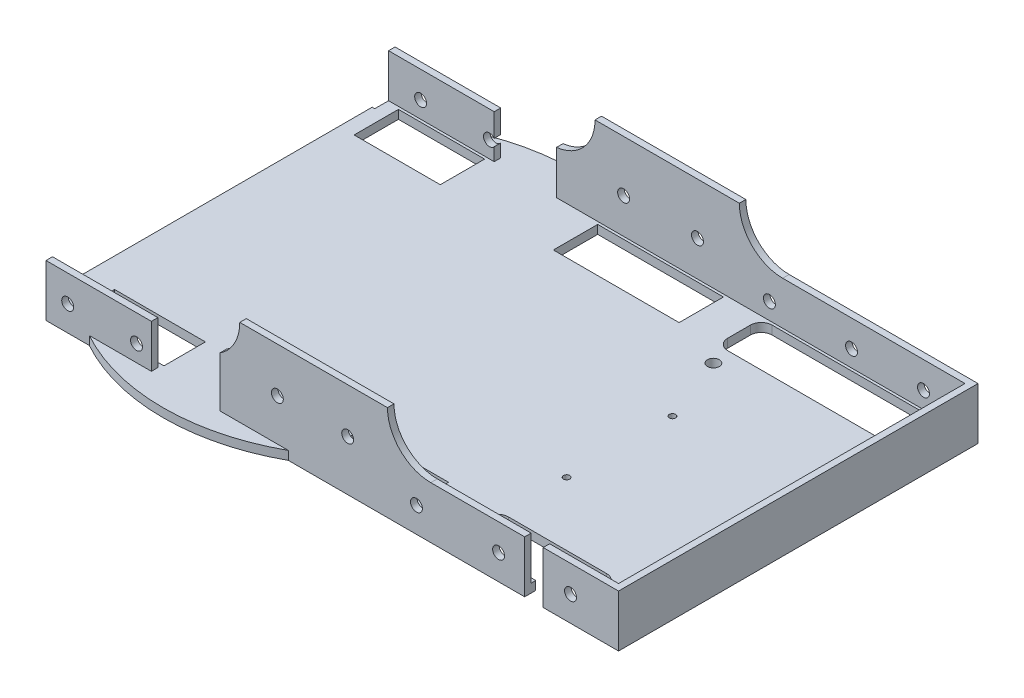
SolidWorks part; units mm, degrees
ref_plane "Front Plane" through (0, 0, 0) normal (0, 0, 1) x (1, 0, 0)
ref_plane "Top Plane" through (0, 0, 0) normal (0, 1, 0) x (1, 0, 0)
ref_plane "Right Plane" through (0, 0, 0) normal (1, 0, 0) x (0, 0, -1)
sketch "Sketch1" plane through (0, 0, 0) normal (0, 1, 0) x (1, 0, 0)
  line L1 (0, 0) -> (278.0499, 0)
  line L2 (0, 0) -> (0, 166.0007)
  line L3 (0, 166.0007) -> (278.0499, 166.0007)
  line L4 (278.0499, 0) -> (278.0499, 166.0007)
extrude "Boss-Extrude1" add sketch "Sketch1" along normal blind 24
sketch "Sketch2" plane through (0, 0, 0) normal (0, -1, 0) x (-1, 0, 0)
  line L1 (-7.6506, 156.6405) -> (14.2402, 156.6405)
  line L2 (-7.6506, 156.6405) -> (-7.6506, 11.5417)
  line L3 (-7.6506, 11.5417) -> (14.2402, 11.5417)
  line L4 (14.2402, 156.6405) -> (14.2402, 11.5417)
extrude "Cut-Extrude1" cut sketch "Sketch2" against normal through all
sketch "Sketch3" plane through (0, 24, 0) normal (0, 1, 0) x (1, 0, 0)
  line L0 (226.9955, 0) -> (226.9955, 3) construction
  line L1 (0, 0) -> (278.0499, 0) construction
  line L2 (278.0499, 166.0007) -> (278.0499, 163.0007) construction
  line L3 (278.0499, 0) -> (278.0499, 166.0007) construction
  line L4 (0, 155.7398) -> (3, 155.7398) construction
  line L5 (0, 166.0007) -> (0, 156.6405) construction
  line L6 (278.0499, 22.4963) -> (275.0499, 22.4963) construction
  line L7 (275.0499, 163.0007) -> (275.0499, 3)
  line L8 (275.0499, 3) -> (3, 3)
  line L9 (3, 3) -> (3, 163.0007)
  line L10 (3, 163.0007) -> (275.0499, 163.0007)
extrude "Cut-Extrude2" cut sketch "Sketch3" against normal blind 20
sketch "Sketch4" plane through (0, 24, 0) normal (0, 1, 0) x (1, 0, 0)
  line L0 (0, 0) -> (278.0499, 0) construction
  line L1 (171.3453, 0) -> (103.1403, 0)
  line L2 (171.3453, 0) -> (171.3453, 3)
  line L3 (171.3453, 3) -> (103.1403, 3)
  line L4 (103.1403, 0) -> (103.1403, 3)
  line L5 (3, 3) -> (275.0499, 3) construction
extrude "Boss-Extrude2" add sketch "Sketch4" along normal blind 20
fillet "Fillet4" radius 20 1 edges at (103.1403, 24, -1.5) type face fillet first side face at (103.1403, 34, -1.5) second side face at (35.3801, 24, -4.8472)
fillet "Fillet5" radius 20 1 edges at (171.3453, 24, -1.5) type face fillet first side face at (145.489, 24, -97.7284) second side face at (171.3453, 34, -1.5)
sketch "Sketch5" plane through (0, 24, 0) normal (0, 1, 0) x (1, 0, 0)
  line L0 (278.0499, 166.0007) -> (0, 166.0007) construction
  line L1 (104.1867, 166.0007) -> (170.8443, 166.0007)
  line L2 (104.1867, 166.0007) -> (104.1867, 163.0007)
  line L3 (104.1867, 163.0007) -> (170.8443, 163.0007)
  line L4 (170.8443, 166.0007) -> (170.8443, 163.0007)
  line L5 (275.0499, 163.0007) -> (3, 163.0007) construction
extrude "Boss-Extrude3" add sketch "Sketch5" along normal blind 20
fillet "Fillet6" radius 20 1 edges at (104.1867, 24, -164.5007) type face fillet first side face at (104.1867, 34, -164.5007) second side face at (35.7289, 24, -161.8806)
fillet "Fillet7" radius 20 1 edges at (170.8443, 24, -164.5007) type face fillet first side face at (170.8443, 34, -164.5007) second side face at (228.8223, 24, -83.0003)
sketch "Sketch6" plane through (0, 0, -163.0007) normal (0, 0, 1) x (1, 0, 0)
  circle A0 centre (151.5064, 20.306) radius 2.75
  circle A1 centre (117.3926, 20.306) radius 2.75
extrude "HolesForBolts1" cut sketch "Sketch6" against normal through all
sketch "Sketch7" plane through (0, 0, -166.0007) normal (0, 0, -1) x (-1, 0, 0)
  circle A0 centre (-23.6542, 11.6758) radius 2.75
  circle A1 centre (-55.4415, 11.6758) radius 2.75
  circle A2 centre (-83.0044, 11.6758) radius 2.75
  circle A3 centre (-184.7276, 11.6758) radius 2.75
  circle A4 centre (-222.6455, 11.6758) radius 2.75
  circle A5 centre (-255.8817, 11.6758) radius 2.75
extrude "Cut-Extrude4" cut sketch "Sketch7" against normal through all
sketch "Sketch8" plane through (0, 0, -3) normal (0, 0, -1) x (-1, 0, 0)
  circle A0 centre (-120.4871, 23.2804) radius 2.75
  circle A1 centre (-152.9663, 23.2804) radius 2.75
extrude "Cut-Extrude5" cut sketch "Sketch8" against normal blind 20
ref_plane "Plane1" through (0, 0, -11.5417) normal (0, 0, 1) x (1, 0, 0)
sketch "Sketch11" plane through (0, 0, 0) normal (0, -1, 0) x (1, 0, 0)
  line L0 (7.6506, -11.5417) -> (0, -11.5417) construction
  line L1 (0, 0) -> (13.6461, 0)
  line L2 (0, 0) -> (0, -11.5417)
  line L3 (0, -11.5417) -> (13.6461, -11.5417)
  line L4 (13.6461, 0) -> (13.6461, -11.5417)
extrude "Cut-Extrude6" cut sketch "Sketch11" against normal through all
sketch "Sketch12" plane through (0, 0, 0) normal (0, -1, 0) x (1, 0, 0)
  line L0 (0, -156.6405) -> (7.6506, -156.6405) construction
  line L1 (0, -166.0007) -> (8.8441, -166.0007)
  line L2 (0, -166.0007) -> (0, -156.6405)
  line L3 (0, -156.6405) -> (8.8441, -156.6405)
  line L4 (8.8441, -166.0007) -> (8.8441, -156.6405)
extrude "Cut-Extrude7" cut sketch "Sketch12" against normal through all
sketch "HolesInLidForPiCover" plane through (0, 0, 0) normal (0, -1, 0) x (1, 0, 0)
  circle A0 centre (223.0138, -141.6086) radius 2.75
  circle A1 centre (223.0138, -22.1297) radius 2.75
ref_point "RasPiBoltPoint2"
ref_point "RasPiBoltPoint3"
ref_point "RasPiBoltPoint4"
sketch "LidHolesForPi" plane through (0, 0, 0) normal (0, -1, 0) x (1, 0, 0)
  circle A0 centre (200.5621, -102.3707) radius 1.455
  circle A1 centre (200.5621, -53.5029) radius 1.455
  circle A2 centre (258.5449, -53.5029) radius 1.455
  circle A3 centre (258.5449, -102.3707) radius 1.455
extrude "Cut-Extrude9" cut sketch "LidHolesForPi" against normal up to surface (4 mm away) up to face at (76.2977, 4, -83.5457)
ref_point "LidHoleForCoverLocation1"
ref_point "LidHoleForCoverLocation2"
sketch "Sketch14" plane through (0, 0, 0) normal (0, -1, 0) x (1, 0, 0)
  circle A0 centre (264.7636, -18.9201) radius 2.75
  circle A1 centre (181.6168, -18.9187) radius 2.75
extrude "Cut-Extrude10" cut sketch "Sketch14" against normal up to surface (4 mm away) up to face at (258.5449, 4, -54.9579)
sketch "Sketch15" plane through (0, 0, 1.7414) normal (0, -1, 0) x (1, 0, 0)
  circle A0 centre (79.5908, -84.8811) radius 95
extrude "PingPongHolder" add sketch "Sketch15" against normal up to surface (4 mm away) up to face at (181.6168, 4, -21.6687)
sketch "Sketch16" plane through (0, 0, 0) normal (0, -1, 0) x (1, 0, 0)
  line L1 (7.6506, -21.0945) -> (-30.4108, -21.0945)
  line L2 (7.6506, -21.0945) -> (7.6506, -147.5505)
  line L3 (7.6506, -147.5505) -> (-30.4108, -147.5505)
  line L4 (-30.4108, -21.0945) -> (-30.4108, -147.5505)
extrude "Cut-Extrude11" cut sketch "Sketch16" against normal up to surface (4 mm away) up to face at (60.2623, 4, -83.4645)
sketch "Sketch17" plane through (0, 0, 0) normal (0, -1, 0) x (1, 0, 0)
  line L1 (182.1244, -161.8248) -> (267.0462, -161.8248)
  line L2 (182.1244, -161.8248) -> (182.1244, -141.3482)
  line L3 (182.1244, -141.3482) -> (267.0462, -141.3482)
  line L4 (267.0462, -161.8248) -> (267.0462, -141.3482)
  line L5 (164.6719, -141.3482) -> (106.6019, -141.3482)
  line L6 (164.6719, -141.3482) -> (164.6719, -161.8248)
  line L7 (164.6719, -161.8248) -> (106.6019, -161.8248)
  line L8 (106.6019, -141.3482) -> (106.6019, -161.8248)
  line L13 (54.374, -141.3482) -> (14.584, -141.3482)
  line L14 (54.374, -141.3482) -> (54.374, -161.8248)
  line L15 (54.374, -161.8248) -> (14.584, -161.8248)
  line L16 (14.584, -141.3482) -> (14.584, -161.8248)
extrude "Cut-Extrude12" cut sketch "Sketch17" against normal up to surface (4 mm away) up to face at (76.2977, 4, -83.5457)
fillet "Fillet8" radius 5 1 edges at (182.1244, 2, -161.8248) type face fillet first side face at (182.1244, 2, -151.5865) second side face at (224.5853, 2, -161.8248)
fillet "Fillet9" radius 5 1 edges at (182.1244, 2, -141.3482) type face fillet first side face at (182.1244, 2, -149.0865) second side face at (224.5853, 2, -141.3482)
fillet "Fillet10" radius 5 1 edges at (267.0462, 2, -161.8248) type face fillet first side face at (227.0853, 2, -161.8248) second side face at (267.0462, 2, -151.5865)
fillet "Fillet11" radius 5 1 edges at (267.0462, 2, -141.3482) type face fillet first side face at (227.0853, 2, -141.3482) second side face at (267.0462, 2, -149.0865)
sketch "Sketch18" plane through (0, 0, 0) normal (0, -1, 0) x (1, 0, 0)
  line L1 (197.9754, -5.1076) -> (253.3194, -5.1076)
  line L2 (197.9754, -5.1076) -> (197.9754, -24.2435)
  line L3 (197.9754, -24.2435) -> (253.3194, -24.2435)
  line L4 (253.3194, -5.1076) -> (253.3194, -24.2435)
  line L5 (175.294, -5.1076) -> (134.149, -5.1076)
  line L6 (175.294, -5.1076) -> (175.294, -24.2435)
  line L7 (175.294, -24.2435) -> (134.149, -24.2435)
  line L8 (134.149, -5.1076) -> (134.149, -24.2435)
  line L13 (63.0138, -5.1076) -> (21.0604, -5.1076)
  line L14 (63.0138, -5.1076) -> (63.0138, -24.2435)
  line L15 (63.0138, -24.2435) -> (21.0604, -24.2435)
  line L16 (21.0604, -5.1076) -> (21.0604, -24.2435)
extrude "Cut-Extrude13" cut sketch "Sketch18" against normal up to surface (4 mm away) up to face at (135.6369, 4, -151.5865)
fillet "Fillet12" radius 5 1 edges at (197.9754, 2, -5.1076) type face fillet first side face at (197.9754, 2, -14.6756) second side face at (225.6474, 2, -5.1076)
fillet "Fillet13" radius 5 1 edges at (197.9754, 2, -24.2435) type face fillet first side face at (197.9754, 2, -17.1756) second side face at (225.6474, 2, -24.2435)
fillet "Fillet14" radius 5 1 edges at (253.3194, 2, -24.2435) type face fillet first side face at (228.1474, 2, -24.2435) second side face at (253.3194, 2, -14.6756)
fillet "Fillet15" radius 5 1 edges at (253.3194, 2, -5.1076) type face fillet first side face at (253.3194, 2, -12.1756) second side face at (228.1474, 2, -5.1076)
sketch "Sketch19" plane through (0, 0, 0) normal (0, -1, 0) x (1, 0, 0)
sketch "Sketch20" plane through (0, 0, 0) normal (0, 0, 1) x (1, 0, 0)
  line L0 (191.3453, 24) -> (278.0499, 24) construction
  line L1 (243.2334, 24) -> (234.6976, 24)
  line L2 (243.2334, 24) -> (243.2334, 0)
  line L3 (243.2334, 0) -> (234.6976, 0)
  line L4 (234.6976, 24) -> (234.6976, 0)
  line L5 (125.5559, 0) -> (278.0499, 0) construction
extrude "Cut-Extrude14" cut sketch "Sketch20" against normal up to surface (5.1076 mm away) up to face at (225.6474, 2, -5.1076)
sketch "Sketch21" plane through (0, 0, 0) normal (0, -1, 0) x (1, 0, 0)
  circle A0 centre (188.7854, -133.0569) radius 2.75
  circle A1 centre (188.0519, -10.1727) radius 2.75
  circle A2 centre (271.9321, -133.0569) radius 2.75
  circle A3 centre (269.9307, -9.7027) radius 2.75
extrude "Cut-Extrude15" cut sketch "Sketch21" against normal up to surface (4 mm away) up to face at (154.7215, 4, -14.6756)
sketch "Sketch22" plane through (0, 24, 0) normal (0, 1, 0) x (1, 0, 0)
  line L0 (13.6461, 0) -> (83.1403, 0) construction
  line L1 (62.3106, 0) -> (93.919, 0)
  line L2 (62.3106, 0) -> (62.3106, 3.4355)
  line L3 (62.3106, 3.4355) -> (93.919, 3.4355)
  line L4 (93.919, 0) -> (93.919, 3.4355)
extrude "Cut-Extrude16" cut sketch "Sketch22" against normal up to surface and the other way up to surface up to face at (79.5908, 4, 5.9302) other way up to face at (137.2428, 44, -1.5)
sketch "Sketch23" plane through (0, 24, 0) normal (0, 1, 0) x (1, 0, 0)
  line L0 (84.1867, 166.0007) -> (8.8441, 166.0007) construction
  line L1 (57.6232, 166.0007) -> (86.4122, 166.0007)
  line L2 (57.6232, 166.0007) -> (57.6232, 162.8065)
  line L3 (57.6232, 162.8065) -> (86.4122, 162.8065)
  line L4 (86.4122, 166.0007) -> (86.4122, 162.8065)
extrude "Cut-Extrude17" cut sketch "Sketch23" against normal up to surface and the other way up to surface up to face at (79.5908, 4, -172.0702) other way up to face at (137.5155, 44, -164.5007)
